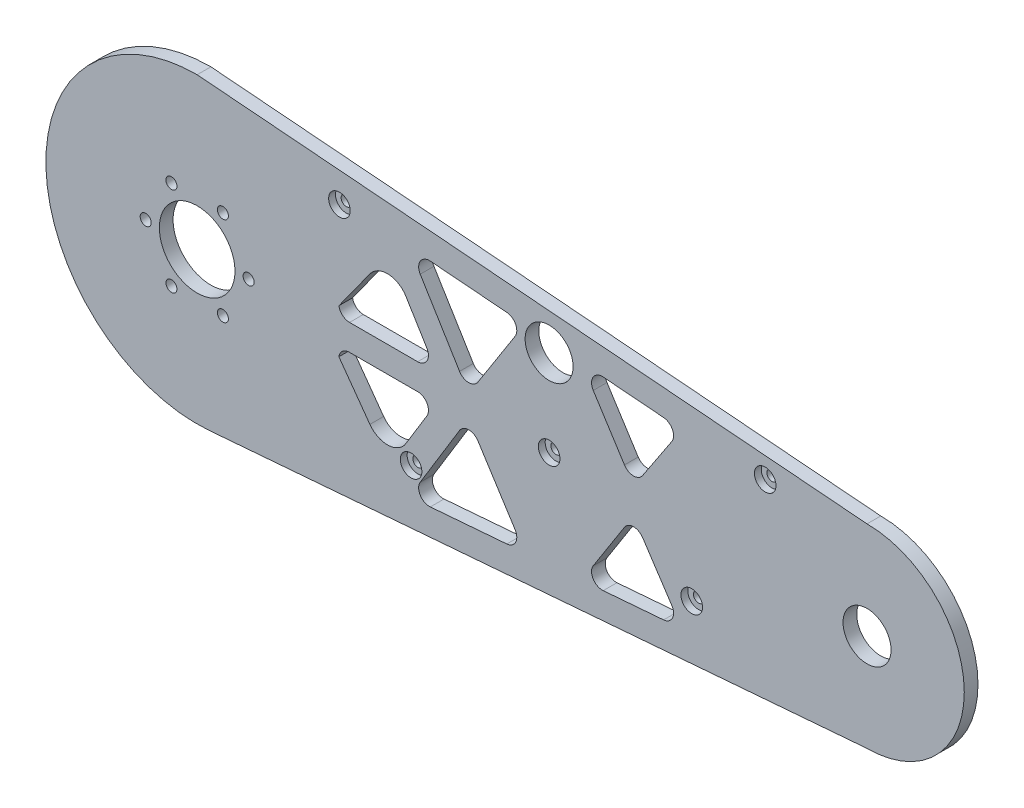
SolidWorks part; units mm, degrees
other "Marca1"
sketch "Croquis3" plane through (-70, -70, 6.35) normal (0, 0, 1) x (1, 0, 0)
material "6061-O (SS)"
ref_plane "Front Plane" through (0, 0, 0) normal (0, 0, 1) x (1, 0, 0)
ref_plane "Top Plane" through (0, 0, 0) normal (0, 1, 0) x (1, 0, 0)
ref_plane "Right Plane" through (0, 0, 0) normal (1, 0, 0) x (0, 0, -1)
sketch "Sketch1" plane through (0, 0, 0) normal (0, 0, 1) x (1, 0, 0)
  line L0 (0, 70) -> (310, 45)
  line L1 (5.1714, -69.8087) -> (310, -45)
  line L2 (0, 0) -> (310, 0) construction
  line L3 (107.899, 49.2595) -> (143.3142, 46.4034)
  line L4 (70.5232, 6) -> (102.03, 6)
  line L5 (219.6238, 32.8105) -> (206.1309, 12.4175)
  line L6 (197.7459, 12.4871) -> (183.2969, 35.1335)
  line L7 (162.8785, 6) -> (162.8785, -6) construction
  line L8 (258.6323, 64.5867) -> (258.6323, 39.5867) construction
  line L9 (147.1275, 38.7303) -> (129.9162, 11.7546)
  line L10 (121.433, 11.8395) -> (103.229, 41.6712)
  line L11 (98.117, 50.0484) -> (42.0027, 50.0484) construction
  line L12 (187.9139, 42.8067) -> (215.8558, 40.5533)
  line L13 (162.8785, 44.8257) -> (162.8785, 6) construction
  line L14 (67.1248, 64.5867) -> (162.8785, 40) construction
  line L15 (201.8849, 6) -> (201.8849, 41.68) construction
  line L16 (125.6066, 5) -> (125.6066, 47.8315) construction
  line L17 (96.5904, 29.5131) -> (106.2981, 13.6045)
  line L18 (125.6066, -5) -> (125.6066, -47.8315) construction
  line L19 (201.8849, -6) -> (201.8849, -41.68) construction
  line L20 (162.8785, -44.8257) -> (162.8785, -6) construction
  line L21 (98.117, -50.0484) -> (42.0027, -50.0484) construction
  line L22 (96.5904, -29.5131) -> (106.2981, -13.6045)
  line L23 (67.1248, 64.5867) -> (409.6974, 64.5867) construction
  line L24 (187.9139, -42.8067) -> (215.8558, -40.5533)
  line L25 (121.433, -11.8395) -> (103.229, -41.6712)
  line L26 (147.1275, -38.7303) -> (129.9162, -11.7546)
  line L27 (162.8785, 0) -> (258.6323, 64.5867) construction
  line L28 (67.1248, 64.5867) -> (67.1248, 39.5867) construction
  line L29 (197.7459, -12.4871) -> (183.2969, -35.1335)
  line L30 (219.6238, -32.8105) -> (206.1309, -12.4175)
  line L31 (70.5232, -6) -> (102.03, -6)
  line L32 (107.899, -49.2595) -> (143.3142, -46.4034)
  line L33 (0, -6.35) -> (0, 6.35) construction
  line L34 (67.1248, 39.5867) -> (162.8785, 40) construction
  line L35 (162.8785, 40) -> (68.3705, 24.1395) construction
  line L36 (79.9417, 30.1512) -> (65.583, 10.2294)
  line L37 (79.9417, -30.1512) -> (65.583, -10.2294)
  arc A0 (65.583, 10.2294) -> (70.5232, 6) centre (70.5232, 11) ccw
  arc A1 (310, -45) -> (310, 45) centre (310, 0) ccw
  circle A2 centre (0, 0) radius 14.2938
  circle A3 centre (310, 0) radius 11.115
  arc A4 (79.9417, 30.1512) -> (96.5904, 29.5131) centre (88.0542, 24.3041) cw
  arc A5 (96.5904, -29.5131) -> (79.9417, -30.1512) centre (88.0542, -24.3041) cw
  arc A6 (0, 70) -> (5.1714, -69.8087) centre (0, 0) ccw
  arc A7 (187.9139, 42.8067) -> (183.2969, 35.1335) centre (187.512, 37.8229) ccw
  arc A8 (219.6238, 32.8105) -> (215.8558, 40.5533) centre (215.4539, 35.5695) ccw
  arc A9 (206.1309, 12.4175) -> (197.7459, 12.4871) centre (201.961, 15.1765) cw
  circle A10 centre (162.8785, 40) radius 11.1125
  arc A13 (102.03, 6) -> (106.2981, 13.6045) centre (102.03, 11) ccw
  arc A14 (121.433, 11.8395) -> (129.9162, 11.7546) centre (125.7011, 14.444) ccw
  arc A15 (147.1275, 38.7303) -> (143.3142, 46.4034) centre (142.9123, 41.4196) ccw
  arc A16 (107.899, 49.2595) -> (103.229, 41.6712) centre (107.4971, 44.2757) ccw
  arc A17 (107.899, -49.2595) -> (103.229, -41.6712) centre (107.4971, -44.2757) cw
  arc A18 (147.1275, -38.7303) -> (143.3142, -46.4034) centre (142.9123, -41.4196) cw
  arc A19 (121.433, -11.8395) -> (129.9162, -11.7546) centre (125.7011, -14.444) cw
  arc A20 (102.03, -6) -> (106.2981, -13.6045) centre (102.03, -11) cw
  arc A24 (206.1309, -12.4175) -> (197.7459, -12.4871) centre (201.961, -15.1765) ccw
  arc A25 (219.6238, -32.8105) -> (215.8558, -40.5533) centre (215.4539, -35.5695) cw
  arc A26 (187.9139, -42.8067) -> (183.2969, -35.1335) centre (187.512, -37.8229) cw
  arc A29 (65.583, -10.2294) -> (70.5232, -6) centre (70.5232, -11) cw
  point P31 (177.8851, 43.6155)
  point P42 (187.6504, 6)
  point P44 (88.7465, 42.3671)
  point P45 (138.1067, 6)
  point P79 (88.7465, -42.3671)
  point P100 (138.1067, -6)
  point P101 (187.6504, -6)
  point P102 (177.8851, -43.6155)
  point P104 (0, 0)
  point P114 (310, 0)
  point P119 (0.2114, 0.3175)
  dimension "D2" = 45
  dimension "D3" = 12.7
  dimension "D4" = 22.23
  dimension "D6" = 12
  dimension "D11" = 5
  dimension "D12" = 70
  dimension "D13" = 25
  dimension "D8" = 5
  dimension "D14" = 12
  dimension "D15" = 25
  dimension "D16" = 310
  dimension "D17" = 22.225
  dimension "D5" = 28.5877
  dimension "D19" = 10
  dimension "D20" = 10
  dimension "D7" = 6
  dimension "D9" = 9.279
  dimension "D10" = 34
  dimension "D18" = 40
extrude "Boss-Extrude1" add sketch "Sketch1" along normal blind 6.35
sketch "Sketch2" plane through (0, 0, 6.35) normal (0, 0, 1) x (1, 0, 0)
  line L0 (263.0927, 39.4927) -> (-0.4655, 64.9983)
  line L1 (4.6885, -64.8307) -> (263.1366, -39.5384)
  arc A0 (-0.4655, 64.9983) -> (4.6885, -64.8307) centre (0, 0) ccw
  arc A1 (263.1366, -39.5384) -> (270.3186, -23.7999) centre (262.1626, -29.5859) ccw
  circle A2 centre (0, 0) radius 40
  arc A3 (270.292, 23.7623) -> (270.3186, -23.7999) centre (303.867, 0) ccw
  arc A4 (270.292, 23.7623) -> (263.0927, 39.4927) centre (262.1295, 29.5392) ccw
  dimension "D1" = 10
  dimension "D2" = 41.133
  dimension "D3" = 65
ref_plane "Plane1" through (0, 0, 10) normal (0, 0, 1) x (1, 0, 0)
sketch "Croquis1" plane through (0, 0, 6.35) normal (0, 0, 1) x (1, 0, 0)
  line L0 (5.1714, -69.8087) -> (310, -45) construction
  line L9 (100.6836, -22.8053) -> (88.7465, -42.3671) construction
  line L10 (96.5904, -29.5131) -> (106.2981, -13.6045) construction
  circle A1 centre (98.9956, -37.0901) radius 2.3813
  circle A2 centre (228.8774, -26.5196) radius 2.3813
  point P20 (0, 0)
  dimension "D5" = 4.7625
  dimension "D1" = 4.7625
extrude "Cortar-Extruir1" cut sketch "Croquis1" against normal blind 50
sketch "Croquis2" plane through (0, 0, 6.35) normal (0, 0, 1) x (1, 0, 0)
  circle A0 centre (98.9956, -37.0901) radius 5
  circle A1 centre (228.8774, -26.5196) radius 5
  dimension "D1" = 10
extrude "Cortar-Extruir2" cut sketch "Croquis2" against normal blind 3.175
sketch "Croquis4" plane through (0, 0, 6.35) normal (0, 0, 1) x (1, 0, 0)
  line L0 (162.8785, 40) -> (162.8785, -40) construction
  line L1 (135.7539, -40) -> (190.0032, -40) construction
  circle A0 centre (162.8785, 0) radius 5
  point P8 (162.8785, -40)
  dimension "D1" = 10
  dimension "D2" = 40
extrude "Cortar-Extruir3" cut sketch "Croquis4" against normal blind 3.175
sketch "Croquis5" plane through (0, 0, 6.35) normal (0, 0, 1) x (1, 0, 0)
  circle A0 centre (162.8785, 0) radius 2.3813
  dimension "D1" = 4.7625
extrude "Cortar-Extruir5" cut sketch "Croquis5" against normal blind 10
sketch "Croquis6" plane through (0, 0, 6.35) normal (0, 0, 1) x (1, 0, 0)
  line L0 (98.9956, -37.0901) -> (228.8774, -26.5196) construction
  line L1 (228.8774, -26.5196) -> (262.8716, 39.2101) construction
  line L2 (98.9956, -37.0901) -> (65.8414, 50.869) construction
  circle A0 centre (65.8414, 50.869) radius 2.3813
  circle A1 centre (262.8716, 39.2101) radius 2.3813
  dimension "D5" = 4.7625
  dimension "D1" = 94
  dimension "D2" = 74
  dimension "D3" = 106
  dimension "D4" = 238
extrude "Cortar-Extruir6" cut sketch "Croquis6" against normal blind 10
sketch "Croquis7" plane through (0, 0, 6.35) normal (0, 0, 1) x (1, 0, 0)
  circle A0 centre (65.8414, 50.869) radius 5
  circle A1 centre (262.8716, 39.2101) radius 5
  dimension "D1" = 10
extrude "Cortar-Extruir7" cut sketch "Croquis7" against normal blind 3.17
sketch "Croquis8" plane through (0, 0, 6.35) normal (0, 0, 1) x (1, 0, 0)
  circle A0 centre (0, 0) radius 17.5
  dimension "D1" = 35
extrude "Cortar-Extruir8" cut sketch "Croquis8" against normal blind 10
sketch "Croquis9" plane through (0, 0, 0) normal (0, 0, -1) x (-1, 0, 0)
  line L0 (0, 0) -> (23.8125, 0) construction
  circle A0 centre (0, 0) radius 23.8125 construction
  circle A1 centre (23.8125, 0) radius 2.5527
  circle A2 centre (11.9062, -20.6222) radius 2.5527
  circle A3 centre (-11.9063, -20.6222) radius 2.5527
  circle A4 centre (-23.8125, 0) radius 2.5527
  circle A5 centre (-11.9062, 20.6222) radius 2.5527
  circle A6 centre (11.9063, 20.6222) radius 2.5527
  point P17 (0, 0)
  dimension "D1" = 47.625
  dimension "D2" = 5.1054
  dimension "D3" = 6
extrude "Cortar-Extruir9" cut sketch "Croquis9" against normal blind 10
